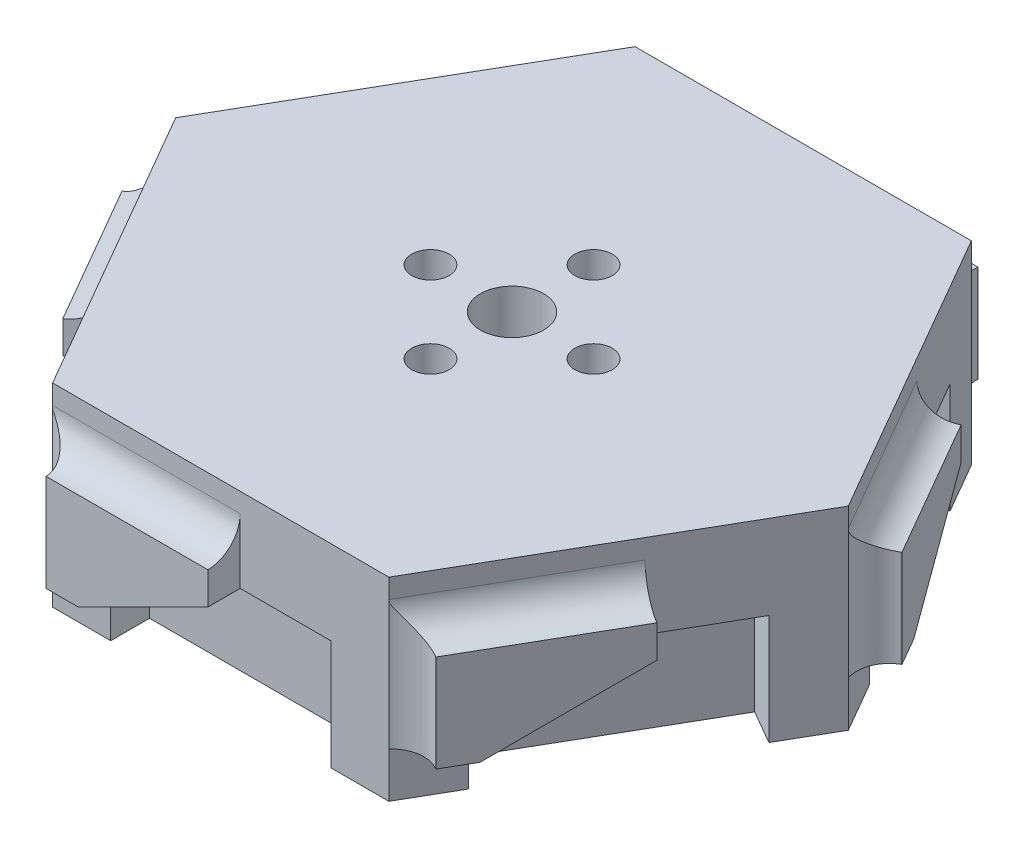
SolidWorks part; units mm, degrees
ref_plane "Front Plane" through (0, 0, 0) normal (0, 0, 1) x (1, 0, 0)
ref_plane "Top Plane" through (0, 0, 0) normal (0, 1, 0) x (1, 0, 0)
ref_plane "Right Plane" through (0, 0, 0) normal (1, 0, 0) x (0, 0, -1)
sketch "Sketch1" plane through (0, 0, 0) normal (0, 1, 0) x (1, 0, 0)
  line L1 (16.4978, 28.575) -> (-16.4978, 28.575)
  line L2 (-16.4978, 28.575) -> (-32.9956, 0)
  line L3 (-32.9956, 0) -> (-16.4978, -28.575)
  line L4 (-16.4978, -28.575) -> (16.4978, -28.575)
  line L5 (16.4978, -28.575) -> (32.9956, 0)
  line L6 (32.9956, 0) -> (16.4978, 28.575)
  circle A0 centre (0, 0) radius 28.575 construction
  dimension "D1" = 57.15
extrude "Boss-Extrude1" add sketch "Sketch1" along normal blind 19.05
sketch "Sketch2" plane through (24.7467, 0, 14.2875) normal (0.866, 0, 0.5) x (0.5, 0, -0.866)
  line L0 (-16.4978, 0) -> (16.4978, 0) construction
  line L1 (0, 0) -> (10.795, 0)
  line L2 (0, 0) -> (0, 10.795)
  line L3 (0, 10.795) -> (10.795, 10.795)
  line L4 (10.795, 0) -> (10.795, 10.795)
  line L6 (0, 0) -> (-10.795, 0)
  line L7 (0, 0) -> (0, 10.795)
  line L8 (0, 10.795) -> (-10.795, 10.795)
  line L9 (-10.795, 0) -> (-10.795, 10.795)
  line M6 (-16.4978, 0) -> (16.4978, 0)
  dimension "D1" = 21.59
  dimension "D2" = 10.795
extrude "Cut-Extrude1" cut sketch "Sketch2" against normal blind 3.81 contours L9 L2 L8 M6 | L4 L3 L2 M6 region at (27.4454, 5.3975, 9.6131) region at (22.0479, 5.3975, 18.9619)
sketch "Sketch3" plane through (24.7467, 0, 14.2875) normal (0.866, 0, 0.5) x (0.5, 0, -0.866)
  line L1 (0, -1000) -> (0, 49000) construction
  line L2 (-13.97, 13.97) -> (-13.97, 4.445)
  line L6 (-10.795, 0) -> (-10.795, 10.795) construction
  line L7 (10.795, 10.795) -> (-10.795, 10.795) construction
  line L12 (1.905, 13.97) -> (-13.97, 13.97)
  line L13 (1.905, 10.795) -> (1.905, 13.97)
  line L14 (-10.795, 4.445) -> (1.905, 10.795)
  line L15 (-13.97, 4.445) -> (-10.795, 4.445)
  point P4 (0, 0)
  dimension "D1" = 3.175
  dimension "D2" = 9.525
  dimension "D3" = 15.875
  dimension "D4" = 3.175
  dimension "D5" = 3.175
  dimension "D6" = 3.175
extrude "Boss-Extrude2" add sketch "Sketch3" along normal blind 3.175
sketch "Sketch4" plane through (0, 0, 0) normal (0, 0, 1) x (1, 0, 0)
  line L0 (0, -1000) -> (0, 49000) construction
pattern_circular "CirPattern1" count 6 over 360 about axis through (0, -1000, 0) along (0, 1, 0) of "Cut-Extrude1", "Boss-Extrude2"
sketch "Sketch6" plane through (0, 19.05, 0) normal (0, 1, 0) x (1, 0, 0)
  line L0 (0, 0) -> (0, 8)
  line L1 (8, 0) -> (0, 0)
  circle A0 centre (0, 0) radius 3.1
  circle A1 centre (0, 8) radius 1.8339
  circle A2 centre (8, 0) radius 1.8339
  circle A3 centre (0, -8) radius 1.8339
  circle A4 centre (-8, 0) radius 1.8339
  point P14 (0, 0)
  dimension "D1" = 6.2
  dimension "D2" = 3.6678
  dimension "D3" = 8
  dimension "D5" = 8
  dimension "D4" = 4
extrude "Cut-Extrude3" cut sketch "Sketch6" against normal through all contours A4 | L0 A0 L1 | A1 | L1 A0 L0 | A2 | A3 region at (-0.4386, 19.05, 0.4386) region at (1.3157, 19.05, -1.3157) region at (-1.2601, 19.05, -9.2601) region at (8, 19.05, -1.782) region at (0, 19.05, 8) region at (-8, 19.05, 0)
fillet "Fillet1" radius 3.175 12 edges at (-13.97, 9.2075, 28.575) (-6.0325, 13.97, 28.575) (-31.7317, 9.2075, 2.1891) (-27.7629, 13.97, 9.0632) (-21.7304, 13.97, -19.5118) (-17.7617, 9.2075, -26.3859) (13.97, 9.2075, -28.575) (6.0325, 13.97, -28.575) (27.7629, 13.97, -9.0632) (31.7317, 9.2075, -2.1891) (21.7304, 13.97, 19.5118) (17.7617, 9.2075, 26.3859)
